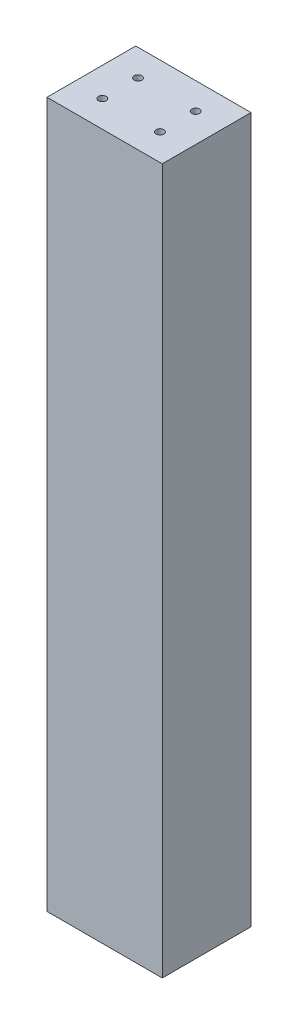
SolidWorks part; units mm, degrees
material "6061 Alloy"
ref_plane "Front Plane" through (0, 0, 0) normal (0, 0, 1) x (1, 0, 0)
ref_plane "Top Plane" through (0, 0, 0) normal (0, 1, 0) x (1, 0, 0)
ref_plane "Right Plane" through (0, 0, 0) normal (1, 0, 0) x (0, 0, -1)
sketch "Sketch1" plane through (0, 0, 0) normal (0, 1, 0) x (1, 0, 0)
  line L1 (0, 0) -> (76.2, 0)
  line L2 (0, 0) -> (0, 58.674)
  line L3 (0, 58.674) -> (76.2, 58.674)
  line L4 (76.2, 0) -> (76.2, 58.674)
  dimension "D1" = 58.674
  dimension "D2" = 76.2
extrude "Boss-Extrude1" add sketch "Sketch1" against normal blind 466.09
sketch "Sketch2" plane through (0, 0, 0) normal (0, 1, 0) x (1, 0, 0)
  line L0 (76.2, 29.337) -> (0, 29.337) construction
  line L1 (76.2, 0) -> (76.2, 58.674) construction
  line L2 (0, 58.674) -> (0, 0) construction
  line L3 (38.1, 0) -> (38.1, 58.674) construction
  line L4 (0, 0) -> (76.2, 0) construction
  line L5 (76.2, 58.674) -> (0, 58.674) construction
  point P12 (57.15, 41.148)
  point P14 (57.15, 17.526)
  point P18 (19.05, 17.526)
  point P19 (19.05, 41.148)
  dimension "D1" = 17.526
  dimension "D2" = 19.05
hole_wizard "1/4-20 Tapped Hole1" positions "3DSketch3" profile "Sketch5" tap size "1/4-20" standard "ANSI Inch" end condition through all
sketch3d "3DSketch3"
  point P0 (57.15, 0, -41.148)
  point P3 (57.15, 0, -17.526)
  point P6 (19.05, 0, -41.148)
  point P9 (19.05, 0, -17.526)
  point P12 (42.8268, 0, -120.8106)
sketch "Sketch5" plane through (57.15, 0, -41.148) normal (1, 0, 0) x (0, 0, 1)
  line L0 (0, 0) -> (0, 466.09)
  line L1 (0, 466.09) -> (2.5527, 466.09)
  line L2 (2.5527, 466.09) -> (2.5527, 0)
  line L5 (2.5527, 0) -> (0, 0)
  line L11 (0, -6.35) -> (0, 107.95) construction
  dimension "Thru Tap Drill Dia." = 5.1054
  dimension "Thru Tap Drill Depth" = 466.09
cosmetic thread "Hole Thread2" parameters "D2"=6.35
cosmetic thread "Hole Thread3" parameters "D2"=6.35
cosmetic thread "Hole Thread4" parameters "D2"=6.35
cosmetic thread "Hole Thread5" parameters "D2"=6.35
